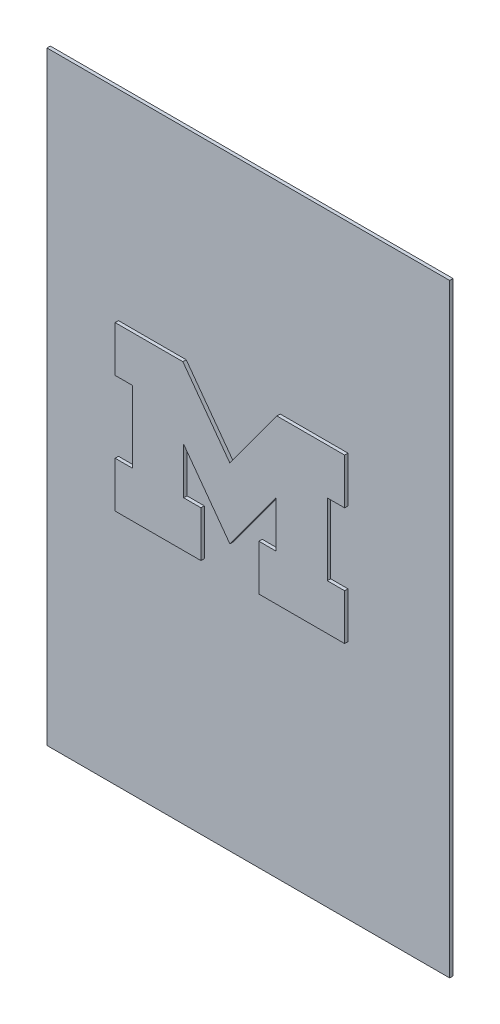
SolidWorks part; units mm, degrees
ref_plane "Front Plane" through (0, 0, 0) normal (0, 0, 1) x (1, 0, 0)
ref_plane "Top Plane" through (0, 0, 0) normal (0, 1, 0) x (1, 0, 0)
ref_plane "Right Plane" through (0, 0, 0) normal (1, 0, 0) x (0, 0, -1)
sketch "Sketch1" plane through (0, 0, 0) normal (0, 0, 1) x (1, 0, 0)
  line L1 (0, 0) -> (304.8, 0)
  line L2 (0, 0) -> (0, 457.2)
  line L3 (0, 457.2) -> (304.8, 457.2)
  line L4 (304.8, 0) -> (304.8, 457.2)
  dimension "D1" = 457.2
  dimension "D2" = 304.8
extrude "Boss-Extrude1" add sketch "Sketch1" along normal blind 2.54
sketch "Sketch3" plane through (0, 0, 2.54) normal (0, 0, 1) x (1, 0, 0)
  line L10 (140.9771, 256.8633) -> (144.0171, 261.0233)
  line L21 (140.9771, 256.8633) -> (137.9371, 261.0233)
  line L24 (54.1163, 216.6153) -> (54.1163, 181.9833)
  line L25 (54.1163, 305.5353) -> (54.1163, 270.9033)
  line L26 (175.9835, 251.8089) -> (140.9771, 203.9054)
  line L27 (227.8379, 305.5353) -> (227.8379, 270.9033)
  line L28 (67.2203, 270.9033) -> (67.2203, 216.6153)
  line L29 (214.7339, 270.9033) -> (214.7339, 216.6153)
  line L30 (119.0747, 216.6153) -> (105.9707, 216.6153)
  line L31 (119.0747, 181.9833) -> (119.0747, 216.6153)
  line L32 (54.1163, 270.9033) -> (67.2203, 270.9033)
  line L33 (105.9707, 251.8089) -> (140.9771, 203.9054)
  line L34 (105.9707, 216.6153) -> (105.9707, 251.8089)
  line L35 (227.8379, 270.9033) -> (214.7339, 270.9033)
  line L36 (162.8795, 216.6153) -> (175.9835, 216.6153)
  line L37 (140.9771, 256.8633) -> (105.4091, 305.5353)
  line L38 (175.9835, 216.6153) -> (175.9835, 251.8089)
  line L39 (176.5451, 305.5353) -> (227.8379, 305.5353)
  line L40 (214.7339, 216.6153) -> (227.8379, 216.6153)
  line L41 (140.9771, 256.8633) -> (176.5451, 305.5353)
  line L42 (227.8379, 216.6153) -> (227.8379, 181.9833)
  line L43 (54.1163, 181.9833) -> (119.0747, 181.9833)
  line L44 (162.8795, 181.9833) -> (162.8795, 216.6153)
  line L45 (227.8379, 181.9833) -> (162.8795, 181.9833)
  line L46 (67.2203, 216.6153) -> (54.1163, 216.6153)
  line L47 (105.4091, 305.5353) -> (54.1163, 305.5353)
extrude "Boss-Extrude3" add sketch "Sketch3" along normal blind 2.54 contours L37 L47 L25 L32 L28 L46 L24 L43 L31 L30 L34 L33 L26 L38 L36 L44 L45 L42 L40 L29 L35 L27 L39 L41 L10 L21 region at (140.9771, 243.6866, 2.54)
